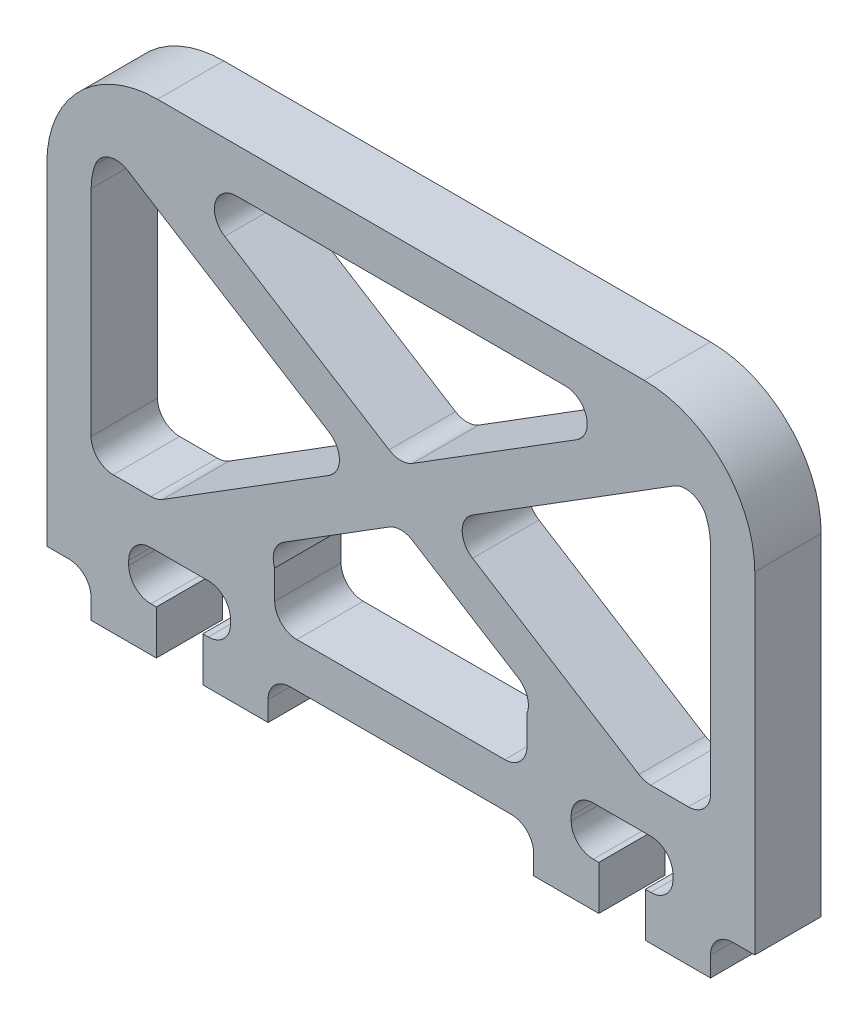
SolidWorks part; units mm, degrees
ref_plane "Front Plane" through (0, 0, 0) normal (0, 0, 1) x (1, 0, 0)
ref_plane "Top Plane" through (0, 0, 0) normal (0, 1, 0) x (1, 0, 0)
ref_plane "Right Plane" through (0, 0, 0) normal (1, 0, 0) x (0, 0, -1)
sketch "Sketch1" plane through (0, 0, 0) normal (0, 0, 1) x (1, 0, 0)
  line L0 (-10, -11.9) -> (-10, 10) construction
  line L1 (-16, 10) -> (16, 10)
  line L2 (-16, 10) -> (-16, -10)
  line L3 (-16, -10) -> (16, -10)
  line L4 (16, 10) -> (16, -10)
  line L5 (-16, 10) -> (16, -10) construction
  line L6 (-16, -10) -> (16, 10) construction
  line L7 (-16, -10) -> (-6, -10)
  line L9 (-14, -11.9) -> (-6, -11.9)
  line L10 (-6, -10) -> (-6, -11.9)
  line L11 (0, 10) -> (0, -10) construction
  line L12 (-11.05, -9.9) -> (-8.95, -9.9)
  line L13 (-11.05, -9.9) -> (-11.05, -11.9)
  line L14 (-11.05, -11.9) -> (-8.95, -11.9)
  line L15 (-8.95, -9.9) -> (-8.95, -11.9)
  line L16 (-11.05, -9.9) -> (-8.95, -11.9) construction
  line L17 (-11.05, -11.9) -> (-8.95, -9.9) construction
  line L18 (-12.3, -7.7) -> (-7.7, -7.7)
  line L19 (-12.3, -7.7) -> (-12.3, -9.9)
  line L20 (-12.3, -9.9) -> (-7.7, -9.9)
  line L21 (-7.7, -7.7) -> (-7.7, -9.9)
  line L22 (-12.3, -7.7) -> (-7.7, -9.9) construction
  line L23 (-12.3, -9.9) -> (-7.7, -7.7) construction
  line L24 (12.3, -7.7) -> (7.7, -7.7)
  line L25 (12.3, -7.7) -> (12.3, -9.9)
  line L26 (12.3, -9.9) -> (7.7, -9.9)
  line L27 (7.7, -7.7) -> (7.7, -9.9)
  line L28 (11.05, -9.9) -> (8.95, -9.9)
  line L29 (11.05, -9.9) -> (11.05, -11.9)
  line L30 (11.05, -11.9) -> (8.95, -11.9)
  line L31 (8.95, -9.9) -> (8.95, -11.9)
  line L32 (16, -10) -> (6, -10)
  line L33 (6, -10) -> (6, -11.9)
  line L34 (14, -11.9) -> (6, -11.9)
  line L36 (-14, -11.9) -> (-14, -10)
  line L37 (14, -11.9) -> (14, -10)
  point P0 (0, 0)
  point P11 (-10, -10.9)
  point P16 (-10, -8.8)
  dimension "D1" = 32
  dimension "D2" = 20
  dimension "D3" = 1.9
  dimension "D4" = 8
  dimension "D5" = 2.1
  dimension "D6" = 2
  dimension "D7" = 2.2
  dimension "D8" = 4.6
  dimension "D9" = 2
extrude "Boss-Extrude2" add sketch "Sketch1" along normal blind 3 contours L31 L26 L27 L24 L25 L29 L3 L4 L1 L2 L13 L20 L19 L18 L21 L15 | L3 L15 L9 L10 | L13 L3 L9 | L34 L31 L3 L33 | L3 L29 L34 region at (0, 0.2943, 0) region at (-12.525, -10.95, 0) region at (12.525, -10.95, 0) region at (-7.475, -10.95, 0) region at (7.475, -10.95, 0)
fillet "Fillet1" radius 5 2 edges at (16, 10, 1.5) (-16, 10, 1.5)
sketch "Sketch2" plane through (0, 0, 3) normal (0, 0, 1) x (1, 0, 0)
  line L0 (-6, -10) -> (6, -10) construction
  line L1 (16, -10) -> (-16, -10)
  line L2 (16, -10) -> (16, 10)
  line L3 (16, 10) -> (-16, 10)
  line L4 (-16, -10) -> (-16, 10)
  line L5 (16, -10) -> (-16, 10) construction
  line L6 (16, 10) -> (-16, -10) construction
  line L8 (16.53, -9.152) -> (-15.47, 10.848)
  line L9 (15.47, 10.848) -> (-16.53, -9.152)
  line L10 (15.47, -10.848) -> (-16.53, 9.152)
  line L11 (16.53, 9.152) -> (-15.47, -10.848)
  line L36 (-16, 5) -> (-16, -10) construction
  line L60 (11, 8) -> (-11, 8)
  line L61 (14, -5.7) -> (14, 5)
  line L62 (-14, -5.7) -> (-5.7, -5.7)
  line L63 (-5.7, -5.7) -> (-5.7, -8)
  line L64 (-5.7, -8) -> (5.7, -8)
  line L65 (5.7, -8) -> (5.7, -5.7)
  line L66 (5.7, -5.7) -> (14, -5.7)
  line L67 (14, -5.7) -> (14, 5)
  line L68 (11, 8) -> (-11, 8)
  line L70 (-14, -5.7) -> (-5.7, -5.7)
  line L71 (-5.7, -5.7) -> (-5.7, -8)
  line L72 (-5.7, -8) -> (5.7, -8)
  line L73 (5.7, -8) -> (5.7, -5.7)
  line L74 (5.7, -5.7) -> (14, -5.7)
  line L80 (-14, 5) -> (-14, -5.7)
  line L81 (-14, 5) -> (-14, -5.7)
  arc A4 (14, 5) -> (11, 8) centre (11, 5) ccw
  arc A5 (14, 5) -> (11, 8) centre (11, 5) ccw
  arc A8 (-11, 8) -> (-14, 5) centre (-11, 5) ccw
  arc A9 (-11, 8) -> (-14, 5) centre (-11, 5) ccw
  point P0 (0, 0)
  dimension "D1" = 1
  dimension "D2" = 1
  dimension "D3" = 2
extrude "Cut-Extrude1" cut sketch "Sketch2" against normal up to next contours L10 L70 L9 | L9 L68 L8 | L11 L8 L74 | L72 L73 L10 L11 L71 region at (0, -5.3754, 3) region at (9.8341, 0.1444, 3) region at (-9.8341, 0.1444, 3) region at (0, 5.7264, 3)
fillet "Fillet2" radius 1 16 edges at (5.7, -8, 1.5) (-5.7, -8, 1.5) (0, -1.1792, 1.5) (11.0068, -5.7, 1.5) (1.8868, 0, 1.5) (10.9132, 8, 1.5) (-10.9132, 8, 1.5) (0, 1.1792, 1.5) (-1.8868, 0, 1.5) (-11.0068, -5.7, 1.5) (14, -5.7, 1.5) (13.1816, 7.0593, 1.5) (-13.1816, 7.0593, 1.5) (-14, -5.7, 1.5) (7.2332, -5.7, 1.5) (-7.2332, -5.7, 1.5)
fillet "Fillet3" radius 1 12 edges at (12.3, -9.9, 1.5) (12.3, -7.7, 1.5) (7.7, -7.7, 1.5) (7.7, -9.9, 1.5) (-12.3, -9.9, 1.5) (-7.7, -9.9, 1.5) (-7.7, -7.7, 1.5) (-12.3, -7.7, 1.5) (14, -10, 1.5) (6, -10, 1.5) (-14, -10, 1.5) (-6, -10, 1.5)
